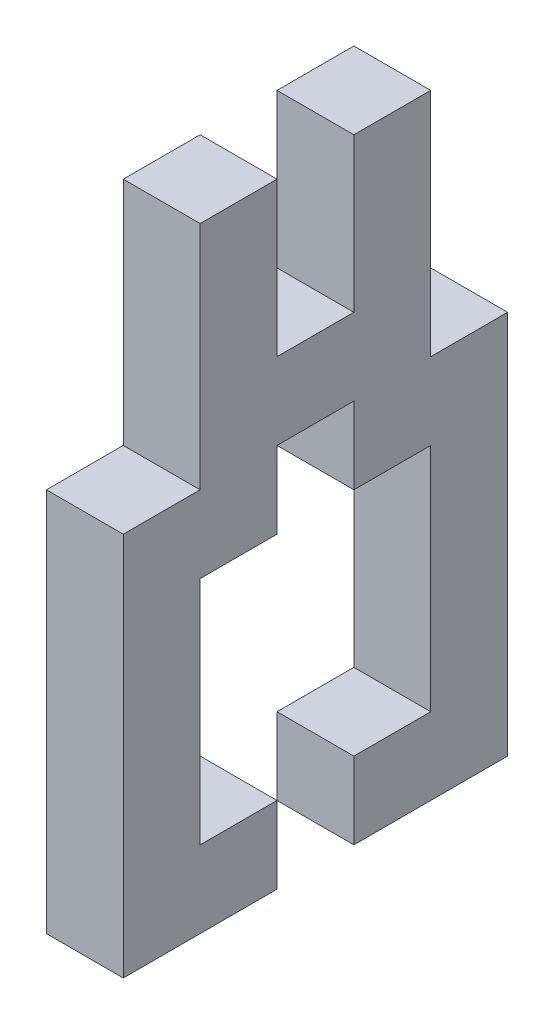
SolidWorks part; units mm, degrees
material "Balsa"
ref_plane "Front Plane" through (0, 0, 0) normal (0, 0, 1) x (1, 0, 0)
ref_plane "Top Plane" through (0, 0, 0) normal (0, 1, 0) x (1, 0, 0)
ref_plane "Right Plane" through (0, 0, 0) normal (1, 0, 0) x (0, 0, -1)
sketch "Sketch2" plane through (0, 0, 0) normal (1, 0, 0) x (0, 0, -1)
  line L2 (12.7, 50.8) -> (12.7, 38.1)
  line L3 (12.7, 38.1) -> (19.05, 38.1)
  line L4 (19.05, 38.1) -> (19.05, 50.8)
  line L5 (19.05, 50.8) -> (25.4, 50.8)
  line L7 (31.75, 0) -> (0, 0)
  line L9 (6.35, 6.35) -> (25.4, 6.35)
  line L10 (6.35, 6.35) -> (6.35, 25.4)
  line L12 (25.4, 6.35) -> (25.4, 25.4)
  line L16 (25.4, 50.8) -> (25.4, 31.75)
  line L17 (25.4, 31.75) -> (31.75, 31.75)
  line L18 (31.75, 31.75) -> (31.75, 0)
  line L20 (6.35, 31.75) -> (0, 31.75)
  line L21 (0, 31.75) -> (0, 0)
  line L22 (12.7, 50.8) -> (6.35, 50.8)
  line L23 (6.35, 50.8) -> (6.35, 31.75)
  line L24 (25.4, 25.4) -> (19.05, 25.4)
  line L25 (19.05, 25.4) -> (19.05, 31.75)
  line L26 (19.05, 31.75) -> (12.7, 31.75)
  line L27 (12.7, 31.75) -> (12.7, 25.4)
  line L28 (12.7, 25.4) -> (6.35, 25.4)
  line L30 (12.7, 6.35) -> (19.05, 6.35)
  line L31 (12.7, 6.35) -> (12.7, 0)
  line L32 (12.7, 0) -> (19.05, 0)
  line L33 (19.05, 6.35) -> (19.05, 0)
  point P13 (15.875, 38.1)
  point P16 (15.875, 0)
  point P26 (15.875, 0)
  point P28 (0, 0)
  dimension "D1" = 6.35
  dimension "D2" = 19.05
  dimension "D3" = 19.05
  dimension "D4" = 6.35
  dimension "D5" = 6.35
  dimension "D6" = 6.35
  dimension "D9" = 6.35
  dimension "D10" = 6.35
  dimension "D7" = 6.35
  dimension "D8" = 6.35
  dimension "D11" = 25.4
  dimension "D12" = 6.35
  dimension "D13" = 6.35
  dimension "D14" = 6.35
extrude "Boss-Extrude1" add sketch "Sketch2" along normal blind 6.35 contours L9 L33 L7 L18 L17 L16 L5 L4 L3 L2 L22 L23 L20 L21 L31 L10 L28 L27 L26 L25 L24 L12 region at (0, 44.45, -12.1009)
equation "\"D2@Sketch2\"=\"D3@Sketch2\""
